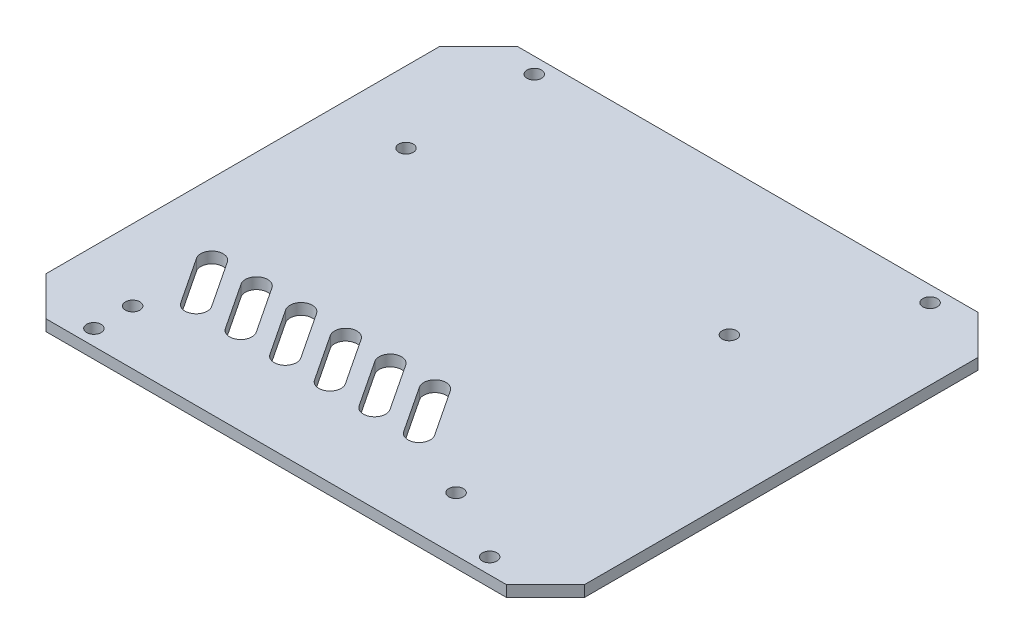
SolidWorks part; units mm, degrees
ref_plane "前视基准面" through (0, 0, 0) normal (0, 0, 1) x (1, 0, 0)
ref_plane "上视基准面" through (0, 0, 0) normal (0, 1, 0) x (1, 0, 0)
ref_plane "右视基准面" through (0, 0, 0) normal (1, 0, 0) x (0, 0, -1)
sketch "草图1" plane through (0, -18.39, 0) normal (0, -1, 0) x (1, 0, 0)
  line L16 (-51.8, -43.2958) -> (-44.7958, -50.3)
  line L17 (-44.7958, -50.3) -> (37.7958, -50.3)
  line L18 (37.7958, -50.3) -> (44.8, -43.2958)
  line L19 (44.8, -43.2958) -> (44.8, 27.2958)
  line L20 (44.8, 27.2958) -> (37.7958, 34.3)
  line L21 (-51.8, 27.2958) -> (-51.8, -43.2958)
  line L22 (37.7958, 34.3) -> (-44.7958, 34.3)
  line L23 (-44.7958, 34.3) -> (-51.8, 27.2958)
  line L24 (-51.8, -43.2958) -> (-44.7958, -50.3)
  line L25 (-44.7958, -50.3) -> (37.7958, -50.3)
  line L26 (37.7958, -50.3) -> (44.8, -43.2958)
  line L27 (44.8, -43.2958) -> (44.8, 27.2958)
  line L28 (44.8, 27.2958) -> (37.7958, 34.3)
  line L29 (-51.8, 27.2958) -> (-51.8, -43.2958)
  line L30 (37.7958, 34.3) -> (-44.7958, 34.3)
  line L31 (-44.7958, 34.3) -> (-51.8, 27.2958)
  dimension "D2" = 96.6
  dimension "D3" = 84.6
  dimension "D1" = 0.2
extrude "凸台-拉伸1" add sketch "草图1" along normal blind 2
sketch "草图2" plane through (0, -20.39, 0) normal (0, -1, 0) x (1, 0, 0)
  circle A0 centre (-39.0116, -24.5) radius 1.3
  circle A1 centre (19, -24.5) radius 1.3
  circle A2 centre (-39.0116, 24.5352) radius 1.3
  circle A3 centre (19, 24.5352) radius 1.3
  dimension "D1" = 2.6
extrude "切除-拉伸1" cut sketch "草图2" against normal up to next
sketch "草图3" plane through (0, -20.39, 0) normal (0, -1, 0) x (1, 0, 0)
  circle A0 centre (32, -47.5) radius 1.3 construction
  circle A1 centre (-39, -47.5) radius 1.3 construction
  circle A2 centre (32, 31.5) radius 1.3 construction
  circle A3 centre (-39, 31.5) radius 1.3 construction
  circle A4 centre (32, -47.5) radius 1.3
  circle A5 centre (-39, -47.5) radius 1.3
  circle A6 centre (32, 31.5) radius 1.3
  circle A7 centre (-39, 31.5) radius 1.3
extrude "切除-拉伸2" cut sketch "草图3" against normal up to next
sketch "草图4" plane through (0, -20.39, 0) normal (0, -1, 0) x (1, 0, 0)
  line L0 (-38.9928, 31.6194) -> (-39.0044, 24.6546) construction
  line L1 (-39.0282, 10.3) -> (-33.5143, 18.6425) construction
  line L2 (-40.6967, 11.4028) -> (-35.1828, 19.7453)
  line L3 (-37.3597, 9.1972) -> (-31.8458, 17.5397)
  line L5 (37.7958, 34.3) -> (-44.7958, 34.3) construction
  line L6 (-31.0282, 10.3) -> (-25.5143, 18.6425) construction
  line L9 (-32.6967, 11.4028) -> (-27.1828, 19.7453)
  line L12 (-29.3597, 9.1972) -> (-23.8458, 17.5397)
  line L15 (-23.0282, 10.3) -> (-17.5143, 18.6425) construction
  line L18 (-24.6967, 11.4028) -> (-19.1828, 19.7453)
  line L21 (-21.3597, 9.1972) -> (-15.8458, 17.5397)
  line L22 (-15.0282, 10.3) -> (-9.5143, 18.6425) construction
  line L23 (-16.6967, 11.4028) -> (-11.1828, 19.7453)
  line L24 (-13.3597, 9.1972) -> (-7.8458, 17.5397)
  line L25 (-7.0282, 10.3) -> (-1.5143, 18.6425) construction
  line L26 (-8.6967, 11.4028) -> (-3.1828, 19.7453)
  line L27 (-5.3597, 9.1972) -> (0.1542, 17.5397)
  line L28 (0.9718, 10.3) -> (6.4857, 18.6425) construction
  line L29 (-0.6967, 11.4028) -> (4.8172, 19.7453)
  line L30 (2.6403, 9.1972) -> (8.1542, 17.5397)
  arc A0 (-40.6967, 11.4028) -> (-37.3597, 9.1972) centre (-39.0282, 10.3) ccw
  arc A1 (-31.8458, 17.5397) -> (-35.1828, 19.7453) centre (-33.5143, 18.6425) ccw
  arc A12 (-32.6967, 11.4028) -> (-29.3597, 9.1972) centre (-31.0282, 10.3) ccw
  arc A13 (-23.8458, 17.5397) -> (-27.1828, 19.7453) centre (-25.5143, 18.6425) ccw
  arc A14 (-24.6967, 11.4028) -> (-21.3597, 9.1972) centre (-23.0282, 10.3) ccw
  arc A15 (-15.8458, 17.5397) -> (-19.1828, 19.7453) centre (-17.5143, 18.6425) ccw
  arc A16 (-16.6967, 11.4028) -> (-13.3597, 9.1972) centre (-15.0282, 10.3) ccw
  arc A17 (-7.8458, 17.5397) -> (-11.1828, 19.7453) centre (-9.5143, 18.6425) ccw
  arc A18 (-8.6967, 11.4028) -> (-5.3597, 9.1972) centre (-7.0282, 10.3) ccw
  arc A19 (0.1542, 17.5397) -> (-3.1828, 19.7453) centre (-1.5143, 18.6425) ccw
  arc A20 (-0.6967, 11.4028) -> (2.6403, 9.1972) centre (0.9718, 10.3) ccw
  arc A21 (8.1542, 17.5397) -> (4.8172, 19.7453) centre (6.4857, 18.6425) ccw
  point P6 (-36.2713, 14.4713)
  point P15 (-28.2713, 14.4713)
  point P22 (-20.2713, 14.4713)
  point P29 (-12.2713, 14.4713)
  point P36 (-4.2713, 14.4713)
  point P43 (3.7287, 14.4713)
  dimension "D1" = 2
  dimension "D2" = 10
  dimension "D3" = 5.5
  dimension "D4" = 12.8
  dimension "D5" = 24
  dimension "D6" = 6
extrude "切除-拉伸3" cut sketch "草图4" against normal up to next
sketch "草图5" plane through (0, -20.39, 0) normal (0, -1, 0) x (1, 0, 0)
sketch_block_instance "块1-1"
sketch_block "块1"
sketch "草图6" plane through (0, -18.39, 0) normal (0, 1, 0) x (1, 0, 0)
  line L0 (-39.0322, 2.6968) -> (-34.8198, 0.2624) construction
  line L1 (-34.177, 0.2624) -> (-29.9873, 2.7014) construction
  line L2 (-29.9828, 3.2622) -> (-34.0539, 5.6966) construction
  line L3 (-29.6682, 9.5398) -> (-30.5435, 10.0367) construction
  line L4 (-30.6757, 9.9592) -> (-30.6757, 7.9487) construction
  line L5 (-30.6301, 7.8712) -> (-29.7548, 7.3788) construction
  line L6 (-29.6226, 7.4564) -> (-29.6226, 9.4623) construction
  line L7 (-33.3108, 9.1249) -> (-33.3108, 8.049) construction
  line L8 (-33.2652, 7.9715) -> (-32.8731, 7.7527) construction
  line L9 (-32.8458, 9.0109) -> (-33.2652, 9.2207) construction
  line L10 (-33.2652, 9.2207) -> (-33.2652, 10.0868) construction
  line L11 (-32.791, 9.8224) -> (-33.2652, 10.0868) construction
  line L12 (-34.3274, 7.7345) -> (-32.823, 6.8819) construction
  line L13 (-34.373, 12.0335) -> (-34.373, 7.8119) construction
  line L14 (-33.3563, 11.6095) -> (-34.2408, 12.111) construction
  line L15 (-33.3108, 10.1644) -> (-33.3108, 11.532) construction
  line L16 (-33.3108, 9.1249) -> (-33.3108, 10.1644) construction
  line L17 (-17.9609, 5.9474) -> (-18.6265, 5.6829) construction
  line L18 (-17.7011, 5.0538) -> (-17.0627, 4.2514) construction
  line L19 (-19.6477, 6.6221) -> (-18.9684, 6.9093) construction
  line L20 (-20.2085, 7.429) -> (-20.9333, 8.3134) construction
  line L21 (-10.1469, 9.1523) -> (-9.7593, 9.1523) construction
  line L22 (-5.5196, 7.1144) -> (-5.5196, 7.7664) construction
  line L23 (-26.0439, 6.3576) -> (-26.0439, 4.2651) construction
  line L24 (-26.0439, 4.2651) -> (-25.2871, 4.2651) construction
  line L25 (-25.2597, 6.3576) -> (-26.0439, 6.3576) construction
  line L26 (-26.7095, 3.7272) -> (-26.7095, 8.979) construction
  line L27 (-26.7095, 8.979) -> (-26.0439, 8.979) construction
  line L28 (-26.0439, 8.979) -> (-26.0439, 6.8956) construction
  line L29 (-26.0439, 6.8956) -> (-25.1731, 6.8956) construction
  line L30 (-25.2096, 3.7272) -> (-26.7095, 3.7272) construction
  line L31 (-33.1558, -0.189) -> (-33.8122, -0.5719) construction
  line L32 (-35.189, -0.5719) -> (-35.8455, -0.189) construction
  line L33 (-35.8455, -0.189) -> (-39.2511, 1.7759) construction
  line L34 (-39.2511, 1.7759) -> (-39.9076, 2.1543) construction
  line L35 (-40.596, 3.3442) -> (-40.596, 8.7967) construction
  line L36 (-39.9076, 9.9866) -> (-39.2511, 10.365) construction
  line L37 (-39.2511, 10.365) -> (-35.8455, 12.3299) construction
  line L38 (-35.8455, 12.3299) -> (-35.189, 12.7128) construction
  line L39 (-33.8122, 12.7128) -> (-33.1558, 12.3299) construction
  line L40 (-33.1558, 12.3299) -> (-29.7503, 10.365) construction
  line L41 (-29.7503, 10.365) -> (-29.0938, 9.9866) construction
  line L42 (-28.4054, 8.7967) -> (-28.4054, 3.3442) construction
  line L43 (-29.0938, 2.1543) -> (-29.7503, 1.7759) construction
  line L44 (-29.7503, 1.7759) -> (-33.1558, -0.189) construction
  line L45 (-5.3737, 8.5687) -> (-5.2826, 8.979) construction
  line L46 (-5.2826, 8.979) -> (-4.2431, 8.979) construction
  line L47 (-4.2431, 8.979) -> (-4.2431, 6.6631) construction
  line L48 (-7.6486, 5.3365) -> (-7.2018, 6.1753) construction
  line L49 (-5.4056, 8.5687) -> (-5.3737, 8.5687) construction
  line L50 (-8.0133, 5.8243) -> (-8.0133, 4.9034) construction
  line L51 (-8.0133, 4.9034) -> (-9.5086, 4.9034) construction
  line L52 (-11.3094, 7.3378) -> (-11.3094, 7.3652) construction
  line L53 (-11.3869, 8.8286) -> (-11.3869, 8.8651) construction
  line L54 (-9.5178, 8.1767) -> (-10.1606, 8.1767) construction
  line L55 (-8.6424, 5.8243) -> (-8.0133, 5.8243) construction
  line L56 (-13.8761, 4.9034) -> (-13.8761, 7.5749) construction
  line L57 (-15.0295, 7.2649) -> (-15.0295, 4.9034) construction
  line L58 (-15.0295, 4.9034) -> (-16.3014, 4.9034) construction
  line L59 (-16.3014, 4.9034) -> (-16.3014, 7.4245) construction
  line L60 (-13.7575, 8.4183) -> (-13.7302, 8.4183) construction
  line L61 (-13.7302, 8.4183) -> (-13.639, 8.979) construction
  line L62 (-13.639, 8.979) -> (-12.5996, 8.979) construction
  line L63 (-12.5996, 8.979) -> (-12.5996, 4.9034) construction
  line L64 (-12.5996, 4.9034) -> (-13.8761, 4.9034) construction
  line L65 (-21.7265, 8.979) -> (-21.7265, 5.0857) construction
  line L66 (-22.3785, 8.979) -> (-21.7265, 8.979) construction
  line L67 (-22.3785, 5.0857) -> (-22.3785, 8.979) construction
  line L68 (-21.7265, 5.0857) -> (-22.3785, 5.0857) construction
  line L69 (-3.4042, 8.979) -> (-2.1368, 8.979) construction
  line L70 (-2.1368, 8.979) -> (-2.1368, 6.6494) construction
  line L71 (-0.8102, 5.9838) -> (-0.596, 4.8851) construction
  line L72 (-2.2508, 5.61) -> (-2.2782, 5.61) construction
  line L73 (-2.2782, 5.61) -> (-2.3648, 4.9034) construction
  line L74 (-2.3648, 4.9034) -> (-3.4042, 4.9034) construction
  line L75 (-3.4042, 4.9034) -> (-3.4042, 8.979) construction
  line L76 (-39.0322, 2.6968) -> (-34.8198, 0.2624)
  line L77 (-34.177, 0.2624) -> (-29.9873, 2.7014)
  line L78 (-29.9828, 3.2622) -> (-34.0539, 5.6966)
  line L79 (-29.6682, 9.5398) -> (-30.5435, 10.0367)
  line L80 (-30.6757, 9.9592) -> (-30.6757, 7.9487)
  line L81 (-30.6301, 7.8712) -> (-29.7548, 7.3788)
  line L82 (-29.6226, 7.4564) -> (-29.6226, 9.4623)
  line L83 (-33.3108, 9.1249) -> (-33.3108, 8.049)
  line L84 (-33.2652, 7.9715) -> (-32.8731, 7.7527)
  line L85 (-32.8458, 9.0109) -> (-33.2652, 9.2207)
  line L86 (-33.2652, 9.2207) -> (-33.2652, 10.0868)
  line L87 (-32.791, 9.8224) -> (-33.2652, 10.0868)
  line L88 (-34.3274, 7.7345) -> (-32.823, 6.8819)
  line L89 (-34.373, 12.0335) -> (-34.373, 7.8119)
  line L90 (-33.3563, 11.6095) -> (-34.2408, 12.111)
  line L91 (-33.3108, 10.1644) -> (-33.3108, 11.532)
  line L92 (-33.3108, 9.1249) -> (-33.3108, 10.1644)
  line L93 (-17.9609, 5.9474) -> (-18.6265, 5.6829)
  line L94 (-17.7011, 5.0538) -> (-17.0627, 4.2514)
  line L95 (-19.6477, 6.6221) -> (-18.9684, 6.9093)
  line L96 (-20.2085, 7.429) -> (-20.9333, 8.3134)
  line L97 (-10.1469, 9.1523) -> (-9.7593, 9.1523)
  line L98 (-5.5196, 7.1144) -> (-5.5196, 7.7664)
  line L99 (-26.0439, 6.3576) -> (-26.0439, 4.2651)
  line L100 (-26.0439, 4.2651) -> (-25.2871, 4.2651)
  line L101 (-25.2597, 6.3576) -> (-26.0439, 6.3576)
  line L102 (-26.7095, 3.7272) -> (-26.7095, 8.979)
  line L103 (-26.7095, 8.979) -> (-26.0439, 8.979)
  line L104 (-26.0439, 8.979) -> (-26.0439, 6.8956)
  line L105 (-26.0439, 6.8956) -> (-25.1731, 6.8956)
  line L106 (-25.2096, 3.7272) -> (-26.7095, 3.7272)
  line L107 (-33.1558, -0.189) -> (-33.8122, -0.5719)
  line L108 (-35.189, -0.5719) -> (-35.8455, -0.189)
  line L109 (-35.8455, -0.189) -> (-39.2511, 1.7759)
  line L110 (-39.2511, 1.7759) -> (-39.9076, 2.1543)
  line L111 (-40.596, 3.3442) -> (-40.596, 8.7967)
  line L112 (-39.9076, 9.9866) -> (-39.2511, 10.365)
  line L113 (-39.2511, 10.365) -> (-35.8455, 12.3299)
  line L114 (-35.8455, 12.3299) -> (-35.189, 12.7128)
  line L115 (-33.8122, 12.7128) -> (-33.1558, 12.3299)
  line L116 (-33.1558, 12.3299) -> (-29.7503, 10.365)
  line L117 (-29.7503, 10.365) -> (-29.0938, 9.9866)
  line L118 (-28.4054, 8.7967) -> (-28.4054, 3.3442)
  line L119 (-29.0938, 2.1543) -> (-29.7503, 1.7759)
  line L120 (-29.7503, 1.7759) -> (-33.1558, -0.189)
  line L121 (-5.3737, 8.5687) -> (-5.2826, 8.979)
  line L122 (-5.2826, 8.979) -> (-4.2431, 8.979)
  line L123 (-4.2431, 8.979) -> (-4.2431, 6.6631)
  line L124 (-7.6486, 5.3365) -> (-7.2018, 6.1753)
  line L125 (-5.4056, 8.5687) -> (-5.3737, 8.5687)
  line L126 (-8.0133, 5.8243) -> (-8.0133, 4.9034)
  line L127 (-8.0133, 4.9034) -> (-9.5086, 4.9034)
  line L128 (-11.3094, 7.3378) -> (-11.3094, 7.3652)
  line L129 (-11.3869, 8.8286) -> (-11.3869, 8.8651)
  line L130 (-9.5178, 8.1767) -> (-10.1606, 8.1767)
  line L131 (-8.6424, 5.8243) -> (-8.0133, 5.8243)
  line L132 (-13.8761, 4.9034) -> (-13.8761, 7.5749)
  line L133 (-15.0295, 7.2649) -> (-15.0295, 4.9034)
  line L134 (-15.0295, 4.9034) -> (-16.3014, 4.9034)
  line L135 (-16.3014, 4.9034) -> (-16.3014, 7.4245)
  line L136 (-13.7575, 8.4183) -> (-13.7302, 8.4183)
  line L137 (-13.7302, 8.4183) -> (-13.639, 8.979)
  line L138 (-13.639, 8.979) -> (-12.5996, 8.979)
  line L139 (-12.5996, 8.979) -> (-12.5996, 4.9034)
  line L140 (-12.5996, 4.9034) -> (-13.8761, 4.9034)
  line L141 (-21.7265, 8.979) -> (-21.7265, 5.0857)
  line L142 (-22.3785, 8.979) -> (-21.7265, 8.979)
  line L143 (-22.3785, 5.0857) -> (-22.3785, 8.979)
  line L144 (-21.7265, 5.0857) -> (-22.3785, 5.0857)
  line L145 (-3.4042, 8.979) -> (-2.1368, 8.979)
  line L146 (-2.1368, 8.979) -> (-2.1368, 6.6494)
  line L147 (-0.8102, 5.9838) -> (-0.596, 4.8851)
  line L148 (-2.2508, 5.61) -> (-2.2782, 5.61)
  line L149 (-2.2782, 5.61) -> (-2.3648, 4.9034)
  line L150 (-2.3648, 4.9034) -> (-3.4042, 4.9034)
  line L151 (-3.4042, 4.9034) -> (-3.4042, 8.979)
  spline S0 degree 3 poles (1947.2043, 259.0221) (-2040.5975, -86.3945) (1971.5647, -86.1046) (-2015.9835, 259.8919) knots -24.014283 -24.014283 -24.014283 -24.014283 31.060476 31.060476 31.060476 31.060476 only from (-34.8198, 0.2624) to (-34.177, 0.2624) construction
  spline S1 degree 3 poles (-178.8618, 1996.4067) (-13.3017, -2002.4803) (85.7628, 2005.1657) (-277.1173, -1980.6649) knots -12.069605 -12.069605 -12.069605 -12.069605 23.053377 23.053377 23.053377 23.053377 only from (-29.9873, 2.7014) to (-29.9828, 3.2622) construction
  spline S2 degree 3 poles (-2011.9647, -280.5218) (1973.0796, 101.2598) (-2042.0834, 101.2623) (1942.99, -280.5143) knots -16.956312 -16.956312 -16.956312 -16.956312 31.955994 31.955994 31.955994 31.955994 only from (-34.0539, 5.6966) to (-34.9429, 5.6966) construction
  spline S3 degree 2 poles (1696.8938, 1005.9909) (-1772.9636, -998.1959) (1692.7429, 1003.6514) knots -19.544322 -19.544322 -19.544322 21.524182 21.524182 21.524182 only from (-34.9429, 5.6966) to (-39.0732, 3.3123) construction
  spline S4 degree 3 poles (312.9236, -1964.6822) (-255.5836, 1997.2947) (39.8207, -2001.4292) (20.6091, 2000.9771) knots -16.033039 -16.033039 -16.033039 -16.033039 19.060221 19.060221 19.060221 19.060221 only from (-39.0732, 3.3123) to (-39.0322, 2.6968) construction
  spline S5 degree 3 poles (1612.1466, 1139.1382) (-173.749, 124.6775) (-29.5451, -1.4055) (-29.5451, 6.2482) (-29.5451, 12.5795) (-131.1047, 41.0713) (891.7703, -1766.7786) knots -20.983072 -20.983072 -20.983072 -20.983072 3 3 3 23.1269 23.1269 23.1269 23.1269 only from (-30.1469, 6.0431) to (-30.1469, 7.1281) construction
  spline S6 degree 3 poles (-1593.6748, -1232.4433) (112.4759, -108.2288) (-30.7532, 14.45) (-30.7532, 6.9321) (-30.7532, 0.2328) (76.6581, -24.0346) (-1002.5668, 1752.6044) knots -22.899222 -22.899222 -22.899222 -22.899222 1 1 1 21.696321 21.696321 21.696321 21.696321 only from (-30.1469, 7.1281) to (-30.1469, 6.0431) construction
  spline S7 degree 3 poles (-1735.267, -1035.1971) (1720.3132, 981.2712) (-1822.079, -884.2768) (1795.5461, 824.5182) knots -24.864003 -24.864003 -24.864003 -24.864003 29.805716 29.805716 29.805716 29.805716 only from (-30.5435, 10.0367) to (-30.6757, 9.9592) construction
  spline S8 degree 3 poles (1803.8452, -787.8206) (-1835.1338, 879.7734) (1736.3613, -937.8925) (-1752.2845, 1025.0132) knots -52.644856 -52.644856 -52.644856 -52.644856 63.422153 63.422153 63.422153 63.422153 only from (-30.6757, 7.9487) to (-30.6301, 7.8712) construction
  spline S9 degree 3 poles (1675.9971, 1050.9308) (-1781.5786, -962.103) (1762.6814, 899.8753) (-1856.6746, -805.2277) knots -20.869425 -20.869425 -20.869425 -20.869425 33.809897 33.809897 33.809897 33.809897 only from (-29.7548, 7.3788) to (-29.6226, 7.4564) construction
  spline S10 degree 3 poles (-1017.153, 1748.416) (898.1967, -1765.8691) (-895.3334, 1815.971) (771.5167, -1822.726) knots -45.73326 -45.73326 -45.73326 -45.73326 46.535072 46.535072 46.535072 46.535072 only from (-29.6226, 9.4623) to (-29.6682, 9.5398) construction
  spline S11 degree 3 poles (1241.4728, -1544.2848) (-126.4363, -19.7603) (-21.5989, 9.5171) (-21.5989, 3.8639) (-21.5989, -3.1211) (-150.7291, 66.7677) (1747.5616, 931.244) knots -20.398043 -20.398043 -20.398043 -20.398043 3 3 3 28.967808 28.967808 28.967808 28.967808 only from (-22.0502, 4.2833) to (-22.0502, 3.44) construction
  spline S12 degree 3 poles (-1791.638, 931.233) (106.6275, 66.7672) (-22.5016, -3.1211) (-22.5016, 3.8639) (-22.5016, 9.5171) (82.3355, -19.7602) (-1285.567, -1544.2778) knots -24.967698 -24.967698 -24.967698 -24.967698 1 1 1 24.398007 24.398007 24.398007 24.398007 only from (-22.0502, 3.44) to (-22.0502, 4.2833) construction
  spline S13 degree 3 poles (953.112, -1731.5311) (-960.0271, 1783.9495) (831.3079, -1798.9714) (-833.3757, 1840.6921) knots -41.715469 -41.715469 -41.715469 -41.715469 50.515238 50.515238 50.515238 50.515238 only from (-33.3108, 8.049) to (-33.2652, 7.9715) construction
  spline S14 degree 3 poles (345.3515, -1953.7628) (-656.074, 2008.4671) (704.4049, -1945.0024) (-795.7723, 1856.1671) knots -18.836401 -18.836401 -18.836401 -18.836401 26.867419 26.867419 26.867419 26.867419 only from (-32.8731, 7.7527) to (-32.0799, 7.9031) construction
  spline S15 degree 3 poles (393.8329, 1947.428) (-1017.3565, -1766.8215) (1294.138, 1559.3727) (-1541.9229, -1298.5467) knots -37.738435 -37.738435 -37.738435 -37.738435 30.849118 30.849118 30.849118 30.849118 only from (-32.0799, 7.9031) to (-32.8458, 9.0109) construction
  spline S16 degree 3 poles (-1970.6267, 490.4514) (1900.3877, -652.3893) (-1909.3139, 822.203) (1735.9268, -921.8099) knots -2.984455 -2.984455 -2.984455 -2.984455 24.908291 24.908291 24.908291 24.908291 only from (-31.0405, 7.315) to (-32.791, 9.8224) construction
  spline S17 degree 3 poles (1301.0551, -1483.1694) (-1380.7778, 1570.3517) (1272.9624, -1585.6466) (-1251.2088, 1591.7607) knots -4.177868 -4.177868 -4.177868 -4.177868 21.267464 21.267464 21.267464 21.267464 only from (-32.823, 6.8819) to (-31.0405, 7.315) construction
  spline S18 degree 3 poles (-426.7908, -1953.0944) (416.9018, 1960.3516) (-543.6183, -1930.3492) (531.9657, 1925.7159) knots -40.574336 -40.574336 -40.574336 -40.574336 54.224541 54.224541 54.224541 54.224541 only from (-34.373, 7.8119) to (-34.3274, 7.7345) construction
  spline S19 degree 3 poles (-1739.7201, -1031.8845) (1717.3311, 982.0362) (-1826.4475, -880.8273) (1792.473, 825.1567) knots -21.867988 -21.867988 -21.867988 -21.867988 32.80886 32.80886 32.80886 32.80886 only from (-34.2408, 12.111) to (-34.373, 12.0335) construction
  spline S20 degree 3 poles (1326.5597, 1477.8337) (-1443.7748, -1422.5109) (1417.5131, 1403.8248) (-1515.2659, -1331.1895) knots -66.611259 -66.611259 -66.611259 -66.611259 68.63044 68.63044 68.63044 68.63044 only from (-33.3108, 11.532) to (-33.3563, 11.6095) construction
  spline S21 degree 3 poles (-1127.9465, 1668.9065) (1205.0665, -1581.8003) (-1320.6139, 1532.1331) (1326.4072, -1474.1074) knots -17.356672 -17.356672 -17.356672 -17.356672 19.212167 19.212167 19.212167 19.212167 only from (-18.6265, 5.6829) to (-19.4334, 5.0857) construction
  spline S22 degree 3 poles (1945.6237, -352.8331) (-1917.2958, 619.5498) (1753.4488, -897.6325) (-1594.6226, 1226.9154) knots -23.773694 -23.773694 -23.773694 -23.773694 31.399142 31.399142 31.399142 31.399142 only from (-19.4334, 5.0857) to (-18.7952, 4.6435) construction
  spline S23 degree 3 poles (-1957.8604, 491.3787) (1905.2875, -332.0334) (-1960.1859, 166.6666) (1980.2936, 44.6676) knots -22.175827 -22.175827 -22.175827 -22.175827 30.019969 30.019969 30.019969 30.019969 only from (-18.7952, 4.6435) to (-17.7011, 5.0538) construction
  spline S24 degree 3 poles (-1996.9289, 274.3391) (2008.3741, -55.5657) (-2041.9478, -141.8187) (1949.9756, 346.3582) knots -14.985955 -14.985955 -14.985955 -14.985955 26.624596 26.624596 26.624596 26.624596 only from (-17.0627, 4.2514) to (-18.7952, 3.5448) construction
  spline S25 degree 3 poles (-959.5674, 1764.5293) (1176.2874, -1603.5878) (-1432.6495, 1427.6748) (1567.7803, -1205.173) knots -7.558703 -7.558703 -7.558703 -7.558703 20.482777 20.482777 20.482777 20.482777 only from (-18.7952, 3.5448) to (-20.7327, 5.1587) construction
  spline S26 degree 3 poles (1924.0493, -458.54) (-2016.5165, 343.495) (1995.4741, -211.501) (-2016.1303, 116.1959) knots -7.852621 -7.852621 -7.852621 -7.852621 24.144848 24.144848 24.144848 24.144848 only from (-20.7327, 5.1587) to (-19.6477, 6.6221) construction
  spline S27 degree 3 poles (615.0637, -1888.8545) (-795.6899, 1841.0297) (868.9978, -1778.6578) (-986.0957, 1757.28) knots -9.138526 -9.138526 -9.138526 -9.138526 27.25787 27.25787 27.25787 27.25787 only from (-18.9684, 6.9093) to (-18.2162, 7.5111) construction
  spline S28 degree 3 poles (215.7009, 1986.9997) (-654.6592, -1923.8751) (894.6606, 1828.6602) (-1110.216, -1665.8008) knots -22.542702 -22.542702 -22.542702 -22.542702 37.658646 37.658646 37.658646 37.658646 only from (-18.2162, 7.5111) to (-18.9137, 7.9761) construction
  spline S29 degree 3 poles (-1605.429, -1208.7716) (1666.7814, 1140.7416) (-1773.5402, -1019.3674) (1765.9801, 905.5471) knots -8.791084 -8.791084 -8.791084 -8.791084 32.386114 32.386114 32.386114 32.386114 only from (-18.9137, 7.9761) to (-20.2085, 7.429) construction
  spline S30 degree 3 poles (1966.5787, -197.5818) (-2051.7497, -0.967) (2002.48, 224.4874) (-1974.8286, -400.794) knots -6.294928 -6.294928 -6.294928 -6.294928 33.756853 33.756853 33.756853 33.756853 only from (-20.9333, 8.3134) to (-18.9411, 9.0793) construction
  spline S31 degree 3 poles (124.1341, -1982.3989) (-457.1442, 1958.1164) (708.8959, -1855.2284) (-1015.0804, 1736.3895) knots 0.697384 0.697384 0.697384 0.697384 28.978211 28.978211 28.978211 28.978211 only from (-18.9411, 9.0793) to (-16.9033, 7.4108) construction
  spline S32 degree 3 poles (-1495.2544, 1354.2838) (1523.5493, -1377.9736) (-1538.1686, 1424.3054) (1353.4505, -1448.6746) knots -4.734801 -4.734801 -4.734801 -4.734801 40.265101 40.265101 40.265101 40.265101 only from (-16.9033, 7.4108) to (-17.9609, 5.9474) construction
  spline S33 degree 3 poles (-1961.8056, -418.0731) (126.6492, -101.6131) (-10.6711, 16.7967) (-10.6711, 6.2847) (-10.6711, -3.9538) (125.3735, 107.9903) (-1932.7785, 547.0377) knots -21.79377 -21.79377 -21.79377 -21.79377 3 3 3 27.67833 27.67833 27.67833 27.67833 only from (-10.156, 6.923) to (-10.156, 5.6556) construction
  spline S34 degree 3 poles (1882.1607, 641.7029) (-158.572, 123.862) (-9.6409, -4.6535) (-9.6409, 6.2847) (-9.6409, 17.5385) (-160.5965, -118.9677) (1923.9331, -488.0552) knots -25.364902 -25.364902 -25.364902 -25.364902 1 1 1 27.543492 27.543492 27.543492 27.543492 only from (-10.156, 5.6556) to (-10.156, 6.923) construction
  spline S35 degree 3 poles (398.3769, -1946.8651) (-621.0655, 1916.7975) (746.5301, -1849.6014) (-860.4662, 1818.6943) knots -20.367991 -20.367991 -20.367991 -20.367991 27.043685 27.043685 27.043685 27.043685 only from (-9.7593, 9.1523) to (-9.1667, 9.4441) construction
  spline S36 degree 3 poles (-1851.6901, 784.2948) (1770.8918, -932.7585) (-1685.1957, 1125.6418) (1512.1872, -1283.8884) knots -14.155704 -14.155704 -14.155704 -14.155704 26.455766 26.455766 26.455766 26.455766 only from (-9.1667, 9.4441) to (-10.0557, 9.8954) construction
  spline S37 degree 3 poles (-1999.7746, -177.9397) (2048.5506, 17.7992) (-2059.7856, 149.4036) (1971.6374, -249.0633) knots -24.53604 -24.53604 -24.53604 -24.53604 22.203045 22.203045 22.203045 22.203045 only from (-10.0557, 9.8954) to (-10.9219, 9.4668) construction
  spline S38 degree 3 poles (335.4233, 1977.3974) (-130.5762, -1935.4278) (-138.8194, 1950.0115) (386.7962, -1948.2187) knots -42.090152 -42.090152 -42.090152 -42.090152 46.007634 46.007634 46.007634 46.007634 only from (-10.9219, 9.4668) to (-10.7304, 9.1021) construction
  spline S39 degree 3 poles (-2000.164, -195.6542) (1968.231, 177.2652) (-1992.5781, -127.132) (1986.8184, 117.9013) knots -23.761314 -23.761314 -23.761314 -23.761314 27.411452 27.411452 27.411452 27.411452 only from (-10.7304, 9.1021) to (-10.1469, 9.1523) construction
  spline S40 degree 3 poles (1900.4815, 611.268) (-1853.5024, -713.4995) (1804.2956, 824.4669) (-1796.5625, -882.5407) knots -25.691977 -25.691977 -25.691977 -25.691977 25.491412 25.491412 25.491412 25.491412 only from (-5.5196, 7.7664) to (-6.135, 8.09) construction
  spline S41 degree 3 poles (-2003.4629, -52.8338) (2017.9029, -136.2777) (-2009.5197, 324.3726) (1939.2706, -450.8338) knots -29.27083 -29.27083 -29.27083 -29.27083 28.779665 28.779665 28.779665 28.779665 only from (-6.135, 8.09) to (-6.5727, 7.739) construction
  spline S42 degree 3 poles (-1965.4656, -395.4958) (1971.7383, 441.6954) (-1983.3474, -426.4496) (1951.4791, 419.1184) knots -18.272249 -18.272249 -18.272249 -18.272249 20.366917 20.366917 20.366917 20.366917 only from (-6.5727, 7.739) to (-5.5196, 7.1144) construction
  spline S43 degree 3 poles (-552.3477, -1916.0072) (39.6444, 1949.1893) (231.1798, -1947.9287) (-488.2476, 1949.0672) knots -16.951569 -16.951569 -16.951569 -16.951569 21.292276 21.292276 21.292276 21.292276 only from (-25.2871, 4.2651) to (-23.9011, 5.2681) construction
  spline S44 degree 3 poles (74.9674, -1978.7796) (-669.1868, 1491.4113) (1220.9961, -1007.5518) (-1925.4997, 576.7533) knots -20.703775 -20.703775 -20.703775 -20.703775 29.911591 29.911591 29.911591 29.911591 only from (-23.9011, 5.2681) to (-25.2597, 6.3576) construction
  spline S45 degree 3 poles (1967.7044, -102.3152) (-2083.6001, -202.2982) (1987.7708, 465.393) (-1913.3422, -643.1952) knots -12.662635 -12.662635 -12.662635 -12.662635 20.708978 20.708978 20.708978 20.708978 only from (-25.1731, 6.8956) to (-23.2401, 5.2681) construction
  spline S46 degree 3 poles (-1462.7137, 1393.5071) (1511.2501, -1404.3078) (-1580.4996, 1407.0991) (1432.7296, -1365.1759) knots -7.615095 -7.615095 -7.615095 -7.615095 23.693651 23.693651 23.693651 23.693651 only from (-23.2401, 5.2681) to (-25.2096, 3.7272) construction
  spline S47 degree 3 poles (-1986.2159, -424.6605) (1872.5149, 650.7296) (-1856.7008, -859.0204) (1668.1443, 1044.8861) knots -40.403395 -40.403395 -40.403395 -40.403395 46.454358 46.454358 46.454358 46.454358 only from (-33.8122, -0.5719) to (-34.5006, -0.7543) construction
  spline S48 degree 3 poles (-1740.3489, 1039.5921) (1790.0962, -854.0172) (-1943.0897, 646.2372) (1918.0006, -420.927) knots -38.373718 -38.373718 -38.373718 -38.373718 48.302597 48.302597 48.302597 48.302597 only from (-34.5006, -0.7543) to (-35.189, -0.5719) construction
  spline S49 degree 3 poles (-754.8971, 1867.8409) (885.9932, -1784.6) (-1157.7277, 1677.1962) (1246.9181, -1524.5355) knots -12.834285 -12.834285 -12.834285 -12.834285 29.798641 29.798641 29.798641 29.798641 only from (-39.9076, 2.1543) to (-40.596, 3.3442) construction
  spline S50 degree 3 poles (1310.7611, 1480.2732) (-1219.4015, -1620.1293) (943.9093, 1763.7167) (-807.2491, -1834.6442) knots -11.169927 -11.169927 -11.169927 -11.169927 32.277267 32.277267 32.277267 32.277267 only from (-40.596, 8.7967) to (-39.9076, 9.9866) construction
  spline S51 degree 3 poles (1829.5545, -704.5958) (-1983.3127, 518.655) (1959.6502, -271.0062) (-2031.7382, 64.4568) knots -28.630568 -28.630568 -28.630568 -28.630568 59.634843 59.634843 59.634843 59.634843 only from (-35.189, 12.7128) to (-34.5006, 12.8952) construction
  spline S52 degree 3 poles (1962.7022, 65.7414) (-2028.2181, -273.3756) (1913.3784, 521.8911) (-1897.0742, -708.4939) knots -29.74703 -29.74703 -29.74703 -29.74703 58.724161 58.724161 58.724161 58.724161 only from (-34.5006, 12.8952) to (-33.8122, 12.7128) construction
  spline S53 degree 3 poles (611.3262, -1882.3455) (-897.4898, 1821.8566) (1049.2417, -1687.0258) (-1295.1838, 1553.5314) knots -2.467628 -2.467628 -2.467628 -2.467628 41.506639 41.506639 41.506639 41.506639 only from (-29.0938, 9.9866) to (-28.4054, 8.7967) construction
  spline S54 degree 3 poles (-1230.5684, -1592.4268) (988.9215, 1738.3623) (-842.904, -1836.9675) (564.0724, 1910.0048) knots -0.095652 -0.095652 -0.095652 -0.095652 42.997123 42.997123 42.997123 42.997123 only from (-28.4054, 3.3442) to (-29.0938, 2.1543) construction
  spline S55 degree 3 poles (-1430.5573, 1407.5659) (1723.1127, -1481.9909) (-1919.6145, 1389.7982) (1763.4855, -917.7581) knots -7.107453 -7.107453 -7.107453 -7.107453 39.300169 39.300169 39.300169 39.300169 only from (-4.2431, 6.6631) to (-5.8934, 4.8031) construction
  spline S56 degree 3 poles (200.3126, 1993.6618) (-113.4143, -2029.6162) (37.9701, 2047.0917) (-46.8978, -1994.2146) knots -24.475698 -24.475698 -24.475698 -24.475698 28.452112 28.452112 28.452112 28.452112 only from (-5.8934, 4.8031) to (-7.6486, 5.3365) construction
  spline S57 degree 3 poles (-1933.6669, -520.0604) (1769.2026, 770.3694) (-1678.914, -975.8177) (1607.9896, 1184.3814) knots -29.345565 -29.345565 -29.345565 -29.345565 33.949512 33.949512 33.949512 33.949512 only from (-7.2018, 6.1753) to (-6.135, 5.8197) construction
  spline S58 degree 3 poles (-1709.7987, 1053.3931) (1749.403, -1046.8479) (-1793.7464, 1008.7473) (1793.1121, -866.6254) knots -20.675466 -20.675466 -20.675466 -20.675466 32.208493 32.208493 32.208493 32.208493 only from (-6.135, 5.8197) to (-5.5196, 6.3394) construction
  spline S59 degree 3 poles (1975.7527, -248.8039) (-1868.9813, 512.6632) (1631.6647, -894.331) (-1295.7423, 1512.4535) knots -12.733532 -12.733532 -12.733532 -12.733532 25.757539 25.757539 25.757539 25.757539 only from (-5.5196, 6.3394) to (-7.7854, 7.8393) construction
  spline S60 degree 3 poles (1042.4421, 1706.8309) (-834.6219, -1820.7719) (589.0356, 1925.2458) (-367.8223, -1955.7065) knots -11.03402 -11.03402 -11.03402 -11.03402 21.264003 21.264003 21.264003 21.264003 only from (-7.7854, 7.8393) to (-6.5727, 9.0793) construction
  spline S61 degree 3 poles (-582.1125, -1906.1013) (523.4678, 1965.3983) (-513.1262, -1956.0805) (513.8823, 1939.9285) knots -17.627726 -17.627726 -17.627726 -17.627726 33.245267 33.245267 33.245267 33.245267 only from (-6.5727, 9.0793) to (-5.4056, 8.5687) construction
  spline S62 degree 3 poles (-1930.5691, 559.3395) (1974.8488, -448.3348) (-2018.9786, 347.7304) (1976.7281, -218.5664) knots -33.500705 -33.500705 -33.500705 -33.500705 55.20773 55.20773 55.20773 55.20773 only from (-9.5086, 4.9034) to (-10.156, 4.8031) construction
  spline S63 degree 3 poles (-1999.2913, 198.6019) (2020.2524, -1.5641) (-2032.1384, -171.0059) (1955.7763, 357.6437) knots -3.872904 -3.872904 -3.872904 -3.872904 23.676976 23.676976 23.676976 23.676976 only from (-10.156, 4.8031) to (-11.8611, 6.2847) construction
  spline S64 degree 3 poles (1939.5115, 440.407) (-1940.4923, -577.4399) (1873.7743, 723.7895) (-1830.7521, -821.4821) knots -8.023341 -8.023341 -8.023341 -8.023341 31.752387 31.752387 31.752387 31.752387 only from (-11.8611, 6.2847) to (-11.3094, 7.3378) construction
  spline S65 degree 3 poles (-1329.9726, 1509.8665) (1428.2205, -1408.3534) (-1547.8279, 1317.3332) (1597.8765, -1177.5524) knots -10.762319 -10.762319 -10.762319 -10.762319 36.904963 36.904963 36.904963 36.904963 only from (-11.3094, 7.3652) to (-11.7608, 8.1265) construction
  spline S66 degree 3 poles (1690.5146, -1041.4074) (-1758.3489, 1014.3497) (1757.9984, -959.3158) (-1776.7351, 948.7003) knots -9.879735 -9.879735 -9.879735 -9.879735 41.23424 41.23424 41.23424 41.23424 only from (-11.7608, 8.1265) to (-11.3869, 8.8286) construction
  spline S67 degree 3 poles (-752.9374, 1842.3255) (1308.8718, -1353.5914) (-1702.759, 958.5145) (1892.0914, -582.47) knots -26.637538 -26.637538 -26.637538 -26.637538 53.487657 53.487657 53.487657 53.487657 only from (-11.3869, 8.8651) to (-11.9659, 9.6674) construction
  spline S68 degree 3 poles (1894.089, -594.3405) (-1996.6922, 519.1508) (2004.2706, -389.5025) (-1990.0486, 289.9866) knots 3.488718 3.488718 3.488718 3.488718 33.266204 33.266204 33.266204 33.266204 only from (-11.9659, 9.6674) to (-10.2563, 10.6932) construction
  spline S69 degree 3 poles (883.5316, -1769.7092) (-1265.933, 1528.3806) (1531.048, -1233.7757) (-1756.2499, 971.1381) knots 2.502912 2.502912 2.502912 2.502912 33.788332 33.788332 33.788332 33.788332 only from (-10.2563, 10.6932) to (-7.9495, 9.2207) construction
  spline S70 degree 3 poles (-1471.0119, 1372.7307) (1578.4938, -1482.6464) (-1566.0618, 1580.68) (1222.054, -1564.0225) knots 0.121158 0.121158 0.121158 0.121158 45.755216 45.755216 45.755216 45.755216 only from (-7.9495, 9.2207) to (-9.5178, 8.1767) construction
  spline S71 degree 3 poles (1988.9699, 46.517) (-2010.5704, -146.5098) (1966.0388, 323.2501) (-1936.5111, -524.1006) knots -22.92357 -22.92357 -22.92357 -22.92357 29.602258 29.602258 29.602258 29.602258 only from (-10.1606, 8.1767) to (-10.7623, 7.9031) construction
  spline S72 degree 3 poles (-533.5031, 1938.1422) (580.6394, -1888.8677) (-675.8787, 1879.566) (733.4353, -1848.486) knots -24.426858 -24.426858 -24.426858 -24.426858 29.596464 29.596464 29.596464 29.596464 only from (-10.7623, 7.9031) to (-10.6347, 7.6159) construction
  spline S73 degree 3 poles (1783.3603, -873.0273) (-1897.0996, 718.9291) (1929.1738, -548.4058) (-1965.9262, 421.9789) knots -49.380783 -49.380783 -49.380783 -49.380783 54.799618 54.799618 54.799618 54.799618 only from (-10.6347, 7.6159) to (-10.156, 7.6889) construction
  spline S74 degree 3 poles (1980.7033, 183.4675) (-2023.5442, -359.0617) (1962.1661, 541.9093) (-1888.572, -672.6294) knots -11.821996 -11.821996 -11.821996 -11.821996 18.874537 18.874537 18.874537 18.874537 only from (-10.156, 7.6889) to (-8.5285, 6.3212) construction
  spline S75 degree 3 poles (-1121.2007, -1655.0713) (1031.1489, 1733.8331) (-972.6532, -1765.1618) (877.4238, 1798.5447) knots -24.892551 -24.892551 -24.892551 -24.892551 35.36044 35.36044 35.36044 35.36044 only from (-8.5285, 6.3212) to (-8.6424, 5.8243) construction
  spline S76 degree 3 poles (1656.0099, -1091.4333) (-1733.7445, 958.5284) (1775.8328, -800.3926) (-1896.9163, 680.7012) knots -21.235065 -21.235065 -21.235065 -21.235065 24.656961 24.656961 24.656961 24.656961 only from (-13.8761, 7.5749) to (-14.5553, 7.9898) construction
  spline S77 degree 3 poles (426.0068, 1957.2742) (-262.0482, -1966.5418) (84.8815, 1999.1955) (-5.2299, -1992.1784) knots -18.599761 -18.599761 -18.599761 -18.599761 21.474642 21.474642 21.474642 21.474642 only from (-14.5553, 7.9898) to (-15.0295, 7.2649) construction
  spline S78 degree 3 poles (-747.2144, 1868.1928) (899.4797, -1926.922) (-1034.2646, 1866.3065) (1043.7125, -1686.9944) knots -15.063115 -15.063115 -15.063115 -15.063115 23.526525 23.526525 23.526525 23.526525 only from (-16.3014, 7.4245) to (-15.034, 9.0793) construction
  spline S79 degree 3 poles (-1430.9478, -1403.3821) (1423.177, 1411.903) (-1498.1835, -1341.8063) (1551.6631, 1251.9189) knots -13.845442 -13.845442 -13.845442 -13.845442 31.313405 31.313405 31.313405 31.313405 only from (-15.034, 9.0793) to (-13.7575, 8.4183) construction
  spline S80 degree 3 poles (1474.4983, 1354.1162) (-1584.5139, -1228.5869) (1669.8836, 1120.5455) (-1739.0959, -982.4011) knots -11.400941 -11.400941 -11.400941 -11.400941 27.863807 27.863807 27.863807 27.863807 only from (-2.1368, 6.6494) to (-1.257, 5.92) construction
  spline S81 degree 3 poles (-1956.5301, 426.4313) (1943.5759, -396.2524) (-1949.6153, 386.5455) (1967.255, -349.6573) knots -19.031705 -19.031705 -19.031705 -19.031705 36.491848 36.491848 36.491848 36.491848 only from (-1.257, 5.92) to (-0.8102, 5.9838) construction
  spline S82 degree 3 poles (1978.5854, -282.24) (-1963.5792, 322.3805) (1959.0024, -335.8715) (-1968.8249, 362.1966) knots -19.114271 -19.114271 -19.114271 -19.114271 38.507502 38.507502 38.507502 38.507502 only from (-0.596, 4.8851) to (-1.0883, 4.8031) construction
  spline S83 degree 3 poles (-1984.9762, 238.8012) (1999.8278, 18.3862) (-1983.2233, -261.3836) (1925.3686, 528.6917) knots -21.685077 -21.685077 -21.685077 -21.685077 21.903976 21.903976 21.903976 21.903976 only from (-1.0883, 4.8031) to (-2.2508, 5.61) construction
  spline S84 degree 3 poles (-34.8198, 0.2624) (-34.6237, 0.1484) (-34.3775, 0.1484) (-34.177, 0.2624) knots 3 3 3 3 4 4 4 4
  spline S85 degree 3 poles (-29.9873, 2.7014) (-29.7731, 2.8245) (-29.7685, 3.1345) (-29.9828, 3.2622) knots 5 5 5 5 6 6 6 6
  spline S86 degree 3 poles (-34.0539, 5.6966) (-34.3274, 5.8562) (-34.6694, 5.8562) (-34.9429, 5.6966) knots 7 7 7 7 8 8 8 8
  spline S87 degree 2 poles (-34.9429, 5.6966) (-39.0641, 3.3169) (-39.0732, 3.3123) knots 0 0 0 1 1 1
  spline S88 degree 3 poles (-39.0732, 3.3123) (-39.2875, 3.1573) (-39.2647, 2.829) (-39.0322, 2.6968) knots 1 1 1 1 2 2 2 2
  spline S89 degree 3 poles (-30.1469, 6.0431) (-29.7958, 5.8425) (-29.5451, 5.9291) (-29.5451, 6.2482) (-29.5451, 6.5628) (-29.7958, 6.9321) (-30.1469, 7.1281) knots 2 2 2 2 3 3 3 4 4 4 4
  spline S90 degree 3 poles (-30.1469, 7.1281) (-30.5024, 7.3333) (-30.7532, 7.2466) (-30.7532, 6.9321) (-30.7532, 6.6084) (-30.5024, 6.2437) (-30.1469, 6.0431) knots 0 0 0 0 1 1 1 2 2 2 2
  spline S91 degree 3 poles (-30.5435, 10.0367) (-30.6028, 10.0686) (-30.6757, 10.0276) (-30.6757, 9.9592) knots 2 2 2 2 3 3 3 3
  spline S92 degree 3 poles (-30.6757, 7.9487) (-30.6757, 7.9168) (-30.6575, 7.8894) (-30.6301, 7.8712) knots 4 4 4 4 5 5 5 5
  spline S93 degree 3 poles (-29.7548, 7.3788) (-29.6956, 7.347) (-29.6226, 7.388) (-29.6226, 7.4564) knots 6 6 6 6 7 7 7 7
  spline S94 degree 3 poles (-29.6226, 9.4623) (-29.6226, 9.4942) (-29.6409, 9.5261) (-29.6682, 9.5398) knots 0 0 0 0 1 1 1 1
  spline S95 degree 3 poles (-22.0502, 4.2833) (-21.7904, 4.2833) (-21.5989, 4.1055) (-21.5989, 3.8639) (-21.5989, 3.5949) (-21.7904, 3.44) (-22.0502, 3.44) knots 2 2 2 2 3 3 3 4 4 4 4
  spline S96 degree 3 poles (-22.0502, 3.44) (-22.3101, 3.44) (-22.5016, 3.5949) (-22.5016, 3.8639) (-22.5016, 4.1055) (-22.3101, 4.2833) (-22.0502, 4.2833) knots 0 0 0 0 1 1 1 2 2 2 2
  spline S97 degree 3 poles (-33.3108, 8.049) (-33.3108, 8.0171) (-33.2926, 7.9852) (-33.2652, 7.9715) knots 4 4 4 4 5 5 5 5
  spline S98 degree 3 poles (-32.8731, 7.7527) (-32.3625, 7.4609) (-32.0799, 7.4564) (-32.0799, 7.9031) knots 6 6 6 6 7 7 7 7
  spline S99 degree 3 poles (-32.0799, 7.9031) (-32.0799, 8.3362) (-32.326, 8.7192) (-32.8458, 9.0109) knots 0 0 0 0 1 1 1 1
  spline S100 degree 3 poles (-31.0405, 7.315) (-31.0405, 8.3682) (-31.8565, 9.2936) (-32.791, 9.8224) knots 10 10 10 10 11 11 11 11
  spline S101 degree 3 poles (-32.823, 6.8819) (-31.8474, 6.3303) (-31.0405, 6.2209) (-31.0405, 7.315) knots 9 9 9 9 10 10 10 10
  spline S102 degree 3 poles (-34.373, 7.8119) (-34.373, 7.78) (-34.3593, 7.7481) (-34.3274, 7.7345) knots 7 7 7 7 8 8 8 8
  spline S103 degree 3 poles (-34.2408, 12.111) (-34.3001, 12.1429) (-34.373, 12.1019) (-34.373, 12.0335) knots 5 5 5 5 6 6 6 6
  spline S104 degree 3 poles (-33.3108, 11.532) (-33.3108, 11.564) (-33.3244, 11.5913) (-33.3563, 11.6095) knots 3 3 3 3 4 4 4 4
  spline S105 degree 3 poles (-18.6265, 5.6829) (-19.0961, 5.496) (-19.4334, 5.382) (-19.4334, 5.0857) knots 1 1 1 1 2 2 2 2
  spline S106 degree 3 poles (-19.4334, 5.0857) (-19.4334, 4.8031) (-19.1918, 4.6435) (-18.7952, 4.6435) knots 2 2 2 2 3 3 3 3
  spline S107 degree 3 poles (-18.7952, 4.6435) (-18.3803, 4.6435) (-18.0521, 4.7848) (-17.7011, 5.0538) knots 3 3 3 3 4 4 4 4
  spline S108 degree 3 poles (-17.0627, 4.2514) (-17.5278, 3.7819) (-18.1797, 3.5448) (-18.7952, 3.5448) knots 5 5 5 5 6 6 6 6
  spline S109 degree 3 poles (-18.7952, 3.5448) (-19.9303, 3.5448) (-20.7327, 4.2651) (-20.7327, 5.1587) knots 6 6 6 6 7 7 7 7
  spline S110 degree 3 poles (-20.7327, 5.1587) (-20.7327, 5.9337) (-20.2085, 6.3987) (-19.6477, 6.6221) knots 7 7 7 7 8 8 8 8
  spline S111 degree 3 poles (-18.9684, 6.9093) (-18.5125, 7.1008) (-18.2162, 7.2011) (-18.2162, 7.5111) knots 9 9 9 9 10 10 10 10
  spline S112 degree 3 poles (-18.2162, 7.5111) (-18.2162, 7.7983) (-18.4395, 7.9761) (-18.9137, 7.9761) knots 10 10 10 10 11 11 11 11
  spline S113 degree 3 poles (-18.9137, 7.9761) (-19.3331, 7.9761) (-19.83, 7.7527) (-20.2085, 7.429) knots 11 11 11 11 12 12 12 12
  spline S114 degree 3 poles (-20.9333, 8.3134) (-20.3817, 8.8195) (-19.634, 9.0793) (-18.9411, 9.0793) knots 13 13 13 13 14 14 14 14
  spline S115 degree 3 poles (-18.9411, 9.0793) (-17.6509, 9.0793) (-16.9033, 8.2998) (-16.9033, 7.4108) knots 14 14 14 14 15 15 15 15
  spline S116 degree 3 poles (-16.9033, 7.4108) (-16.9033, 6.6586) (-17.2998, 6.2118) (-17.9609, 5.9474) knots 15 15 15 15 16 16 16 16
  spline S117 degree 3 poles (-10.156, 6.923) (-10.4477, 6.923) (-10.6711, 6.7087) (-10.6711, 6.2847) (-10.6711, 5.8698) (-10.4477, 5.6556) (-10.156, 5.6556) knots 2 2 2 2 3 3 3 4 4 4 4
  spline S118 degree 3 poles (-10.156, 5.6556) (-9.8551, 5.6556) (-9.6409, 5.8698) (-9.6409, 6.2847) (-9.6409, 6.7087) (-9.8551, 6.923) (-10.156, 6.923) knots 0 0 0 0 1 1 1 2 2 2 2
  spline S119 degree 3 poles (-9.7593, 9.1523) (-9.381, 9.1523) (-9.1667, 9.2024) (-9.1667, 9.4441) knots 4 4 4 4 5 5 5 5
  spline S120 degree 3 poles (-9.1667, 9.4441) (-9.1667, 9.7039) (-9.5314, 9.8954) (-10.0557, 9.8954) knots 5 5 5 5 6 6 6 6
  spline S121 degree 3 poles (-10.0557, 9.8954) (-10.58, 9.8954) (-10.9219, 9.7541) (-10.9219, 9.4668) knots 0 0 0 0 1 1 1 1
  spline S122 degree 3 poles (-10.9219, 9.4668) (-10.9219, 9.3301) (-10.8581, 9.2161) (-10.7304, 9.1021) knots 1 1 1 1 2 2 2 2
  spline S123 degree 3 poles (-10.7304, 9.1021) (-10.5982, 9.1386) (-10.4432, 9.1523) (-10.1469, 9.1523) knots 2 2 2 2 3 3 3 3
  spline S124 degree 3 poles (-5.5196, 7.7664) (-5.7065, 7.967) (-5.8752, 8.09) (-6.135, 8.09) knots 0 0 0 0 1 1 1 1
  spline S125 degree 3 poles (-6.135, 8.09) (-6.3995, 8.09) (-6.5727, 7.9761) (-6.5727, 7.739) knots 1 1 1 1 2 2 2 2
  spline S126 degree 3 poles (-6.5727, 7.739) (-6.5727, 7.4518) (-6.3128, 7.2239) (-5.5196, 7.1144) knots 2 2 2 2 3 3 3 3
  spline S127 degree 3 poles (-25.2871, 4.2651) (-24.3662, 4.2651) (-23.9011, 4.5067) (-23.9011, 5.2681) knots 3 3 3 3 4 4 4 4
  spline S128 degree 3 poles (-23.9011, 5.2681) (-23.9011, 6.0203) (-24.3343, 6.3576) (-25.2597, 6.3576) knots 4 4 4 4 5 5 5 5
  spline S129 degree 3 poles (-25.1731, 6.8956) (-24.0288, 6.8956) (-23.2401, 6.3759) (-23.2401, 5.2681) knots 5 5 5 5 6 6 6 6
  spline S130 degree 3 poles (-23.2401, 5.2681) (-23.2401, 4.1192) (-24.0288, 3.7272) (-25.2096, 3.7272) knots 6 6 6 6 7 7 7 7
  spline S131 degree 3 poles (-33.8122, -0.5719) (-34.0265, -0.6904) (-34.2636, -0.7543) (-34.5006, -0.7543) knots 3 3 3 3 4 4 4 4
  spline S132 degree 3 poles (-34.5006, -0.7543) (-34.7377, -0.7543) (-34.9748, -0.6904) (-35.189, -0.5719) knots 4 4 4 4 5 5 5 5
  spline S133 degree 3 poles (-39.9076, 2.1543) (-40.3315, 2.4005) (-40.596, 2.8564) (-40.596, 3.3442) knots 8 8 8 8 9 9 9 9
  spline S134 degree 3 poles (-40.596, 8.7967) (-40.596, 9.289) (-40.3315, 9.7404) (-39.9076, 9.9866) knots 10 10 10 10 11 11 11 11
  spline S135 degree 3 poles (-35.189, 12.7128) (-34.9748, 12.8359) (-34.7377, 12.8952) (-34.5006, 12.8952) knots 14 14 14 14 15 15 15 15
  spline S136 degree 3 poles (-34.5006, 12.8952) (-34.2636, 12.8952) (-34.0265, 12.8359) (-33.8122, 12.7128) knots 15 15 15 15 16 16 16 16
  spline S137 degree 3 poles (-29.0938, 9.9866) (-28.6652, 9.7404) (-28.4054, 9.289) (-28.4054, 8.7967) knots 19 19 19 19 20 20 20 20
  spline S138 degree 3 poles (-28.4054, 3.3442) (-28.4054, 2.8564) (-28.6652, 2.4005) (-29.0938, 2.1543) knots 21 21 21 21 22 22 22 22
  spline S139 degree 3 poles (-4.2431, 6.6631) (-4.2431, 5.3866) (-4.8403, 4.8031) (-5.8934, 4.8031) knots 11 11 11 11 12 12 12 12
  spline S140 degree 3 poles (-5.8934, 4.8031) (-6.5271, 4.8031) (-7.1106, 5.0173) (-7.6486, 5.3365) knots 0 0 0 0 1 1 1 1
  spline S141 degree 3 poles (-7.2018, 6.1753) (-6.796, 5.9474) (-6.4587, 5.8197) (-6.135, 5.8197) knots 2 2 2 2 3 3 3 3
  spline S142 degree 3 poles (-6.135, 5.8197) (-5.7202, 5.8197) (-5.5469, 6.0112) (-5.5196, 6.3394) knots 3 3 3 3 4 4 4 4
  spline S143 degree 3 poles (-5.5196, 6.3394) (-7.1106, 6.5127) (-7.7854, 6.9777) (-7.7854, 7.8393) knots 4 4 4 4 5 5 5 5
  spline S144 degree 3 poles (-7.7854, 7.8393) (-7.7854, 8.5186) (-7.3249, 9.0793) (-6.5727, 9.0793) knots 5 5 5 5 6 6 6 6
  spline S145 degree 3 poles (-6.5727, 9.0793) (-6.1213, 9.0793) (-5.743, 8.8696) (-5.4056, 8.5687) knots 6 6 6 6 7 7 7 7
  spline S146 degree 3 poles (-9.5086, 4.9034) (-9.6956, 4.835) (-9.9189, 4.8031) (-10.156, 4.8031) knots 9 9 9 9 10 10 10 10
  spline S147 degree 3 poles (-10.156, 4.8031) (-11.0359, 4.8031) (-11.8611, 5.2863) (-11.8611, 6.2847) knots 10 10 10 10 11 11 11 11
  spline S148 degree 3 poles (-11.8611, 6.2847) (-11.8611, 6.7588) (-11.5966, 7.1372) (-11.3094, 7.3378) knots 11 11 11 11 12 12 12 12
  spline S149 degree 3 poles (-11.3094, 7.3652) (-11.5738, 7.5521) (-11.7608, 7.8393) (-11.7608, 8.1265) knots 13 13 13 13 14 14 14 14
  spline S150 degree 3 poles (-11.7608, 8.1265) (-11.7608, 8.4684) (-11.6012, 8.6827) (-11.3869, 8.8286) knots 14 14 14 14 15 15 15 15
  spline S151 degree 3 poles (-11.3869, 8.8651) (-11.7653, 9.0566) (-11.9659, 9.3301) (-11.9659, 9.6674) knots 16 16 16 16 17 17 17 17
  spline S152 degree 3 poles (-11.9659, 9.6674) (-11.9659, 10.3969) (-11.1955, 10.6932) (-10.2563, 10.6932) knots 17 17 17 17 18 18 18 18
  spline S153 degree 3 poles (-10.2563, 10.6932) (-8.8385, 10.6932) (-7.9495, 10.0823) (-7.9495, 9.2207) knots 18 18 18 18 19 19 19 19
  spline S154 degree 3 poles (-7.9495, 9.2207) (-7.9495, 8.4821) (-8.5148, 8.1767) (-9.5178, 8.1767) knots 19 19 19 19 20 20 20 20
  spline S155 degree 3 poles (-10.1606, 8.1767) (-10.5982, 8.1767) (-10.7623, 8.09) (-10.7623, 7.9031) knots 1 1 1 1 2 2 2 2
  spline S156 degree 3 poles (-10.7623, 7.9031) (-10.7623, 7.7664) (-10.7304, 7.7025) (-10.6347, 7.6159) knots 2 2 2 2 3 3 3 3
  spline S157 degree 3 poles (-10.6347, 7.6159) (-10.4569, 7.6661) (-10.2928, 7.6889) (-10.156, 7.6889) knots 3 3 3 3 4 4 4 4
  spline S158 degree 3 poles (-10.156, 7.6889) (-9.2534, 7.6889) (-8.5285, 7.274) (-8.5285, 6.3212) knots 4 4 4 4 5 5 5 5
  spline S159 degree 3 poles (-8.5285, 6.3212) (-8.5285, 6.1251) (-8.5786, 5.9382) (-8.6424, 5.8243) knots 5 5 5 5 6 6 6 6
  spline S160 degree 3 poles (-13.8761, 7.5749) (-14.0903, 7.8758) (-14.2682, 7.9898) (-14.5553, 7.9898) knots 1 1 1 1 2 2 2 2
  spline S161 degree 3 poles (-14.5553, 7.9898) (-14.8791, 7.9898) (-15.0295, 7.8302) (-15.0295, 7.2649) knots 2 2 2 2 3 3 3 3
  spline S162 degree 3 poles (-16.3014, 7.4245) (-16.3014, 8.4411) (-15.923, 9.0793) (-15.034, 9.0793) knots 6 6 6 6 7 7 7 7
  spline S163 degree 3 poles (-15.034, 9.0793) (-14.4779, 9.0793) (-14.0949, 8.8195) (-13.7575, 8.4183) knots 7 7 7 7 8 8 8 8
  spline S164 degree 3 poles (-2.1368, 6.6494) (-1.9226, 6.1115) (-1.5578, 5.92) (-1.257, 5.92) knots 7 7 7 7 8 8 8 8
  spline S165 degree 3 poles (-1.257, 5.92) (-1.0746, 5.92) (-0.9561, 5.9474) (-0.8102, 5.9838) knots 8 8 8 8 9 9 9 9
  spline S166 degree 3 poles (-0.596, 4.8851) (-0.7099, 4.835) (-0.8467, 4.8031) (-1.0883, 4.8031) knots 10 10 10 10 11 11 11 11
  spline S167 degree 3 poles (-1.0883, 4.8031) (-1.4986, 4.8031) (-1.95, 5.0675) (-2.2508, 5.61) knots 0 0 0 0 1 1 1 1
